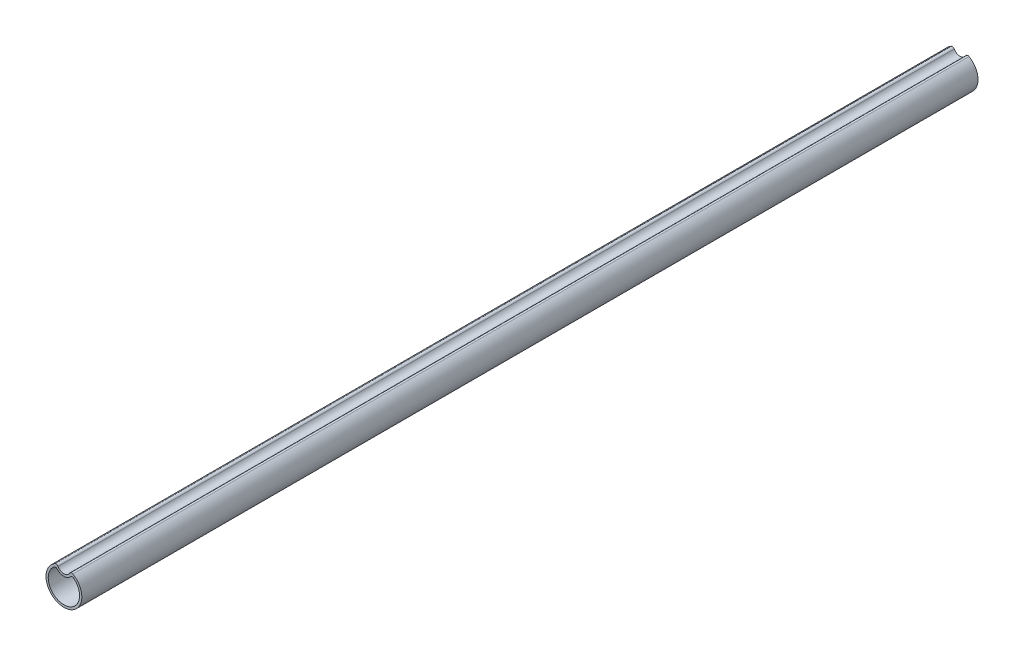
SolidWorks part; units mm, degrees
ref_plane "Piano frontale" through (0, 0, 0) normal (0, 0, 1) x (1, 0, 0)
ref_plane "Piano superiore" through (0, 0, 0) normal (0, 1, 0) x (1, 0, 0)
ref_plane "Piano destro" through (0, 0, 0) normal (1, 0, 0) x (0, 0, -1)
sketch "Schizzo1" plane through (0, 0, 0) normal (0, 0, 1) x (1, 0, 0)
  line L0 (55, 0) -> (-55, 0) construction
  line L1 (0, -55) -> (0, 55) construction
  arc A0 (-1.9997, 3.4643) -> (1.9997, 3.4643) centre (0, 0) ccw
  arc A1 (-2.1848, 2.7344) -> (2.1848, 2.7344) centre (0, 0) ccw
  arc A2 (-1.3123, 3.2734) -> (1.3123, 3.2734) centre (0, 4) ccw
  arc A3 (-1.4981, 2.675) -> (1.4981, 2.675) centre (0, 4) ccw
  arc A4 (-2.1848, 2.7344) -> (-1.4981, 2.675) centre (-1.8727, 2.3438) cw
  circle A5 centre (0, 4) radius 2 construction
  circle A6 centre (0, 4) radius 1.5 construction
  circle A7 centre (0, 0) radius 4 construction
  circle A8 centre (0, 0) radius 3.5 construction
  arc A9 (2.1848, 2.7344) -> (1.4981, 2.675) centre (1.8727, 2.3438) ccw
  arc A10 (1.9997, 3.4643) -> (1.3123, 3.2734) centre (1.7497, 3.0313) ccw
  arc A11 (-1.9997, 3.4643) -> (-1.3123, 3.2734) centre (-1.7497, 3.0313) cw
  point P1 (3.5, 0)
  point P6 (3.8252, 1.1695)
  point P8 (1.4345, 4.4386)
  point P9 (2, 4)
  dimension "D1" = 8
  dimension "D3" = 3
  dimension "D5" = 0.5
  dimension "D2" = 0.5
  dimension "D4" = 0.5
extrude "Estrusione-Estrusione1" add sketch "Schizzo1" along normal blind 200
sketch "Schizzo2" plane through (0, 0, 0) normal (1, 0, 0) x (0, 0, -1)
  line L1 (4.4, 0) -> (-4.4, 0) construction
  line L2 (-183, 1) -> (-177, 1)
  line L4 (-183, -1) -> (-177, -1)
  line L8 (-180, -0.609) -> (-180, 0.4009) construction
  line L9 (0, 4.1422) -> (0, -4.1422) construction
  circle A0 centre (-7, 0) radius 1.5
  arc A1 (-183, 1) -> (-183, -1) centre (-183, 0) ccw
  arc A2 (-177, 1) -> (-177, -1) centre (-177, 0) cw
  point P4 (-180, 0)
  dimension "D1" = 3
  dimension "D6" = 1
  dimension "D2" = 7
  dimension "D3" = 2
  dimension "D4" = 177
  dimension "D5" = 180
  dimension "D7" = 6
extrude "Taglio-Estrusione1" cut sketch "Schizzo2" against normal blind 200
sketch "Schizzo3" plane through (0, 0, 0) normal (0, 1, 0) x (1, 0, 0)
  line L0 (-1.3123, -200) -> (1.3123, -200) construction
  line L1 (0, -55) -> (0, 55) construction
  circle A0 centre (0, -190) radius 1
  point P2 (0, -200)
  dimension "D1" = 2
  dimension "D2" = 10
extrude "Taglio-Estrusione2" cut sketch "Schizzo3" against normal blind 200
ref_axis "Assi1" through (0, -7.3699, 190) along (0, 1, 0)
ref_axis "Assi2" through (-4, 0, 7) along (1, 0, 0)
